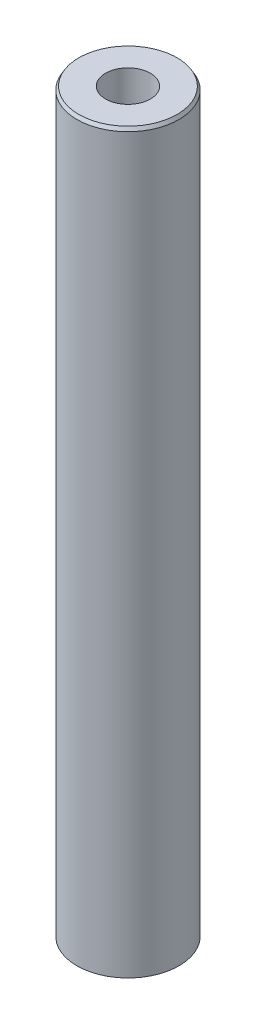
SolidWorks part; units mm, degrees
ref_plane "Front Plane" through (0, 0, 0) normal (0, 0, 1) x (1, 0, 0)
ref_plane "Top Plane" through (0, 0, 0) normal (0, 1, 0) x (1, 0, 0)
ref_plane "Right Plane" through (0, 0, 0) normal (1, 0, 0) x (0, 0, -1)
sketch "Sketch1" plane through (0, 0, 0) normal (0, 1, 0) x (1, 0, 0)
  circle A0 centre (0, 0) radius 35
  dimension "SHAFT_OD" = 70
extrude "Boss-Extrude1" add sketch "Sketch1" along normal blind 505.7895
sketch "Sketch2" plane through (0, 0, 0) normal (0, 1, 0) x (1, 0, 0)
  circle A0 centre (0, 0) radius 15.3493
  dimension "BORE_D" = 30.6986
extrude "Cut-Extrude1" cut sketch "Sketch2" along normal through all
chamfer "Chamfer1" distance 2.3305 angle 30 2 edges at (0, 505.7895, 35) (0, 0, 35) first distance on face at (0, 505.7895, 35) first distance on face at (0, 0, 15.3493)
